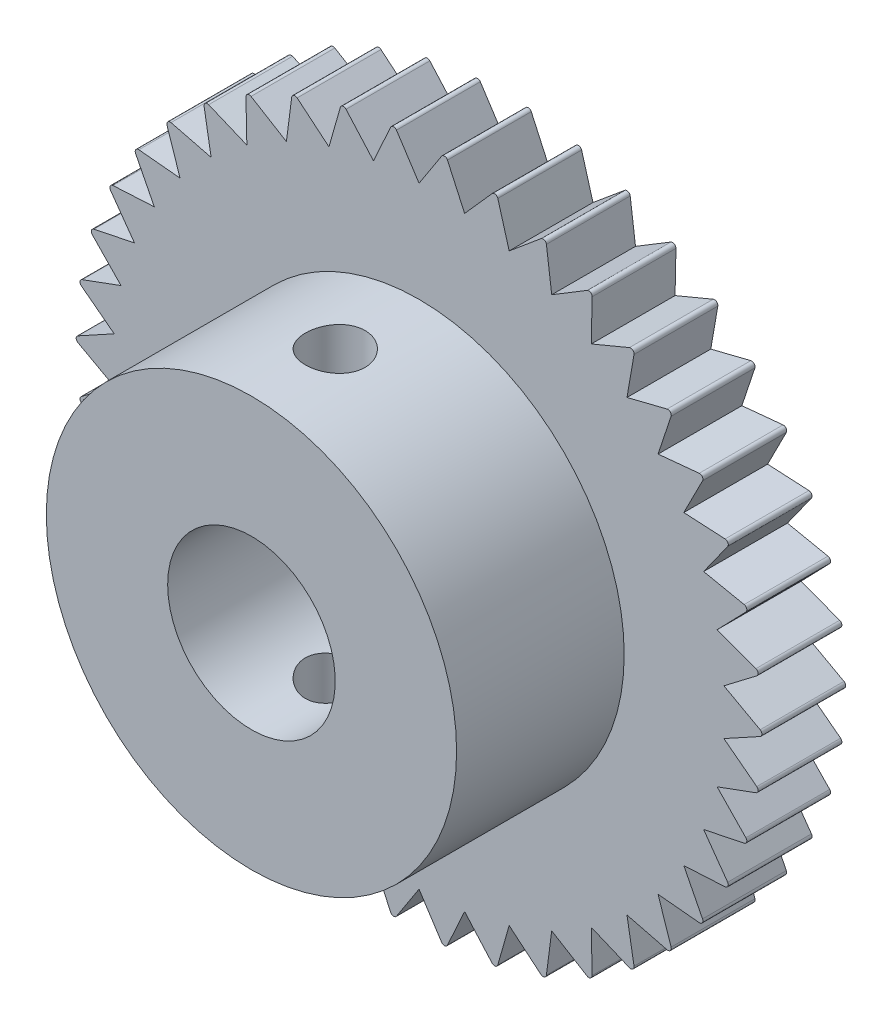
SolidWorks part; units mm, degrees
ref_plane "Front Plane" through (0, 0, 0) normal (0, 0, 1) x (1, 0, 0)
ref_plane "Top Plane" through (0, 0, 0) normal (0, 1, 0) x (1, 0, 0)
ref_plane "Right Plane" through (0, 0, 0) normal (1, 0, 0) x (0, 0, -1)
sketch "Sketch2" plane through (0, 0, 0) normal (1, 0, 0) x (0, 0, -1)
  line L0 (0, 3.175) -> (0, 13.1826)
  line L1 (0, 13.1826) -> (-3.175, 13.1826)
  line L2 (-3.175, 13.1826) -> (-3.175, 7.7724)
  line L3 (-3.175, 7.7724) -> (-9.525, 7.7724)
  line L4 (-9.525, 7.7724) -> (-9.525, 3.175)
  line L5 (-9.525, 3.175) -> (0, 3.175)
  line L6 (6.7854, 0) -> (-20.99, 0) construction
  dimension "D1" = 3.175
  dimension "D2" = 3.175
  dimension "D3" = 9.525
  dimension "D4" = 7.7724
  dimension "D5" = 13.1826
revolve "Revolve1" add sketch "Sketch2" angle 360 about L6
sketch "Sketch3" plane through (0, 0, 3.175) normal (0, 0, 1) x (1, 0, 0)
  line L1 (1.7263, 11.453) -> (0.9543, 13.148)
  line L2 (0, 11.5824) -> (1.016, 13.1434)
  line L3 (0, 11.5824) -> (-1.016, 13.1434)
  line L4 (1.7263, 11.453) -> (2.9636, 12.8452)
  line L5 (3.414, 11.0678) -> (2.9032, 12.8589)
  line L6 (3.414, 11.0678) -> (4.8449, 12.26)
  line L7 (5.0254, 10.4354) -> (4.7873, 12.2826)
  line L8 (5.0254, 10.4354) -> (6.6181, 11.401)
  line L9 (6.5246, 9.5698) -> (6.5645, 11.4319)
  line L10 (6.5246, 9.5698) -> (8.2434, 10.2872)
  line L11 (7.878, 8.4905) -> (8.195, 10.3258)
  line L12 (7.878, 8.4905) -> (9.6846, 8.9437)
  line L13 (9.0555, 7.2215) -> (9.6425, 8.9891)
  line L14 (9.0555, 7.2215) -> (10.9094, 7.4004)
  line L15 (10.0307, 5.7912) -> (10.8745, 7.4516)
  line L16 (10.0307, 5.7912) -> (11.8905, 5.6918)
  line L17 (10.7818, 4.2315) -> (11.8636, 5.7476)
  line L18 (10.7818, 4.2315) -> (12.606, 3.8561)
  line L19 (11.292, 2.5773) -> (12.5878, 3.9152)
  line L20 (11.292, 2.5773) -> (13.0399, 1.9342)
  line L21 (11.55, 0.8656) -> (13.0307, 1.9954)
  line L22 (11.55, 0.8656) -> (13.1826, -0.031)
  line L23 (11.55, -0.8656) -> (13.1826, 0.031)
  line L24 (11.55, -0.8656) -> (13.0307, -1.9954)
  line L25 (11.292, -2.5773) -> (13.0399, -1.9342)
  line L26 (11.292, -2.5773) -> (12.5878, -3.9152)
  line L27 (10.7818, -4.2315) -> (12.606, -3.8561)
  line L28 (10.7818, -4.2315) -> (11.8636, -5.7476)
  line L29 (10.0307, -5.7912) -> (11.8905, -5.6918)
  line L30 (10.0307, -5.7912) -> (10.8745, -7.4516)
  line L31 (9.0555, -7.2215) -> (10.9094, -7.4004)
  line L32 (9.0555, -7.2215) -> (9.6425, -8.9891)
  line L33 (7.878, -8.4905) -> (9.6846, -8.9437)
  line L34 (7.878, -8.4905) -> (8.195, -10.3258)
  line L35 (6.5246, -9.5698) -> (8.2434, -10.2872)
  line L36 (6.5246, -9.5698) -> (6.5645, -11.4319)
  line L37 (5.0254, -10.4354) -> (6.6181, -11.401)
  line L38 (5.0254, -10.4354) -> (4.7873, -12.2826)
  line L39 (3.414, -11.0678) -> (4.8449, -12.26)
  line L40 (3.414, -11.0678) -> (2.9032, -12.8589)
  line L41 (1.7263, -11.453) -> (2.9636, -12.8452)
  line L42 (1.7263, -11.453) -> (0.9543, -13.148)
  line L43 (0, -11.5824) -> (1.016, -13.1434)
  line L44 (0, -11.5824) -> (-1.016, -13.1434)
  line L45 (-1.7263, -11.453) -> (-0.9543, -13.148)
  line L46 (-1.7263, -11.453) -> (-2.9636, -12.8452)
  line L47 (-3.414, -11.0678) -> (-2.9032, -12.8589)
  line L48 (-3.414, -11.0678) -> (-4.8449, -12.26)
  line L49 (-5.0254, -10.4354) -> (-4.7873, -12.2826)
  line L50 (-5.0254, -10.4354) -> (-6.6181, -11.401)
  line L51 (-6.5246, -9.5698) -> (-6.5645, -11.4319)
  line L52 (-6.5246, -9.5698) -> (-8.2434, -10.2872)
  line L53 (-7.878, -8.4905) -> (-8.195, -10.3258)
  line L54 (-7.878, -8.4905) -> (-9.6846, -8.9437)
  line L55 (-9.0555, -7.2215) -> (-9.6425, -8.9891)
  line L56 (-9.0555, -7.2215) -> (-10.9094, -7.4004)
  line L57 (-10.0307, -5.7912) -> (-10.8745, -7.4516)
  line L58 (-10.0307, -5.7912) -> (-11.8905, -5.6918)
  line L59 (-10.7818, -4.2315) -> (-11.8636, -5.7476)
  line L60 (-10.7818, -4.2315) -> (-12.606, -3.8561)
  line L61 (-11.292, -2.5773) -> (-12.5878, -3.9152)
  line L62 (-11.292, -2.5773) -> (-13.0399, -1.9342)
  line L63 (-11.55, -0.8656) -> (-13.0307, -1.9954)
  line L64 (-11.55, -0.8656) -> (-13.1826, 0.031)
  line L65 (-11.55, 0.8656) -> (-13.1826, -0.031)
  line L66 (-11.55, 0.8656) -> (-13.0307, 1.9954)
  line L67 (-11.292, 2.5773) -> (-13.0399, 1.9342)
  line L68 (-11.292, 2.5773) -> (-12.5878, 3.9152)
  line L69 (-10.7818, 4.2315) -> (-12.606, 3.8561)
  line L70 (-10.7818, 4.2315) -> (-11.8636, 5.7476)
  line L71 (-10.0307, 5.7912) -> (-11.8905, 5.6918)
  line L72 (-10.0307, 5.7912) -> (-10.8745, 7.4516)
  line L73 (-9.0555, 7.2215) -> (-10.9094, 7.4004)
  line L74 (-9.0555, 7.2215) -> (-9.6425, 8.9891)
  line L75 (-7.878, 8.4905) -> (-9.6846, 8.9437)
  line L76 (-7.878, 8.4905) -> (-8.195, 10.3258)
  line L77 (-6.5246, 9.5698) -> (-8.2434, 10.2872)
  line L78 (-6.5246, 9.5698) -> (-6.5645, 11.4319)
  line L79 (-5.0254, 10.4354) -> (-6.6181, 11.401)
  line L80 (-5.0254, 10.4354) -> (-4.7873, 12.2826)
  line L81 (-3.414, 11.0678) -> (-4.8449, 12.26)
  line L82 (-3.414, 11.0678) -> (-2.9032, 12.8589)
  line L83 (-1.7263, 11.453) -> (-2.9636, 12.8452)
  line L84 (-1.7263, 11.453) -> (-0.9543, 13.148)
  circle A0 centre (0, 0) radius 13.1826 construction
  circle M1 centre (0, 0) radius 7.7724
  dimension "D1" = 42
  dimension "D3" = 2.032
extrude "Cut-Extrude3" cut sketch "Sketch3" against normal through all and the other way through all flip side to cut contours L84 L83 L82 L81 L80 L79 L78 L77 L76 L75 L74 L73 L72 L71 L70 L69 L68 L67 L66 L65 L64 L63 L62 L61 L60 L59 L58 L57 L56 L55 L54 L53 L52 L51 L50 L49 L48 L47 L46 L45 L44 L43 L42 L41 L40 L39 L38 L37 L36 L35 L34 | M1 region at (2.6007, 11.8788, 3.175) region at (0, 0, 3.175)
fillet "Fillet1" radius 0.127 42 edges at (-10.8454, -7.3943, 1.5875) (-11.8263, -5.6952, 1.5875) (-12.543, -3.869, 1.5875) (-12.9796, -1.9564, 1.5875) (-13.1262, 0, 1.5875) (-12.9796, 1.9564, 1.5875) (-12.543, 3.869, 1.5875) (-11.8263, 5.6952, 1.5875) (-10.8454, 7.3943, 1.5875) (-9.6222, 8.9281, 1.5875) (-8.1841, 10.2625, 1.5875) (-6.5631, 11.3676, 1.5875) (-4.7955, 12.2188, 1.5875) (-2.9209, 12.7971, 1.5875) (-0.9809, 13.0895, 1.5875) (0.9809, 13.0895, 1.5875) (2.9209, 12.7971, 1.5875) (4.7955, 12.2188, 1.5875) (6.5631, 11.3676, 1.5875) (8.1841, 10.2625, 1.5875) (9.6222, 8.9281, 1.5875) (10.8454, 7.3943, 1.5875) (11.8263, 5.6952, 1.5875) (12.543, 3.869, 1.5875) (12.9796, 1.9564, 1.5875) (13.1262, 0, 1.5875) (12.9796, -1.9564, 1.5875) (-9.6222, -8.9281, 1.5875) (-8.1841, -10.2625, 1.5875) (-6.5631, -11.3676, 1.5875) (-4.7955, -12.2188, 1.5875) (-2.9209, -12.7971, 1.5875) (-0.9809, -13.0895, 1.5875) (0.9809, -13.0895, 1.5875) (2.9209, -12.7971, 1.5875) (4.7955, -12.2188, 1.5875) (6.5631, -11.3676, 1.5875) (8.1841, -10.2625, 1.5875) (9.6222, -8.9281, 1.5875) (10.8454, -7.3943, 1.5875) (11.8263, -5.6952, 1.5875) (12.543, -3.869, 1.5875)
sketch "Sketch4" plane through (0, 0, 0) normal (0, 1, 0) x (1, 0, 0)
  line L0 (-7.7724, -9.525) -> (7.7724, -9.525) construction
  circle A0 centre (0, -6.35) radius 1.1303
  dimension "D2" = 2.2606
  dimension "D1" = 3.175
extrude "Cut-Extrude4" cut sketch "Sketch4" against normal through all and the other way through all
cosmetic thread "Cosmetic Thread1" parameters "D2"=2.8448
cosmetic thread "Cosmetic Thread2" parameters "D2"=2.8448
